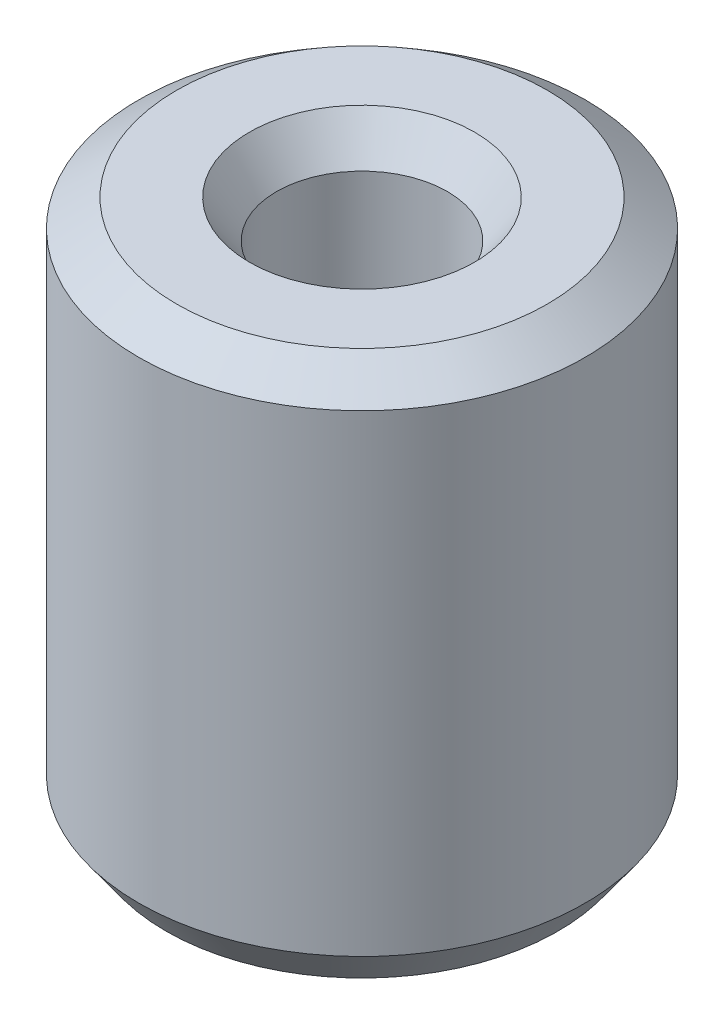
SolidWorks part; units mm, degrees
ref_plane "Front Plane" through (0, 0, 0) normal (0, 0, 1) x (1, 0, 0)
ref_plane "Top Plane" through (0, 0, 0) normal (0, 1, 0) x (1, 0, 0)
ref_plane "Right Plane" through (0, 0, 0) normal (1, 0, 0) x (0, 0, -1)
sketch "Sketch1" plane through (0, 0, 0) normal (0, 1, 0) x (1, 0, 0)
  circle A0 centre (0, 0) radius 32.5
  dimension "SLEEVE_OD" = 65
extrude "Boss-Extrude1" add sketch "Sketch1" along normal blind 78.3015
sketch "Sketch2" plane through (0, 0, 0) normal (0, 1, 0) x (1, 0, 0)
  circle A0 centre (0, 0) radius 12.4488
  dimension "BORE_D" = 24.8976
extrude "Cut-Extrude1" cut sketch "Sketch2" along normal through all
chamfer "Chamfer1" distance 3.9577 angle 54.337 4 edges at (0, 78.3015, 12.4488) (0, 0, 12.4488) (0, 0, 32.5) (0, 78.3015, 32.5) first distance on face at (0, 78.3015, 12.4488) first distance on face at (0, 0, 12.4488) first distance on face at (0, 78.3015, 32.5)
